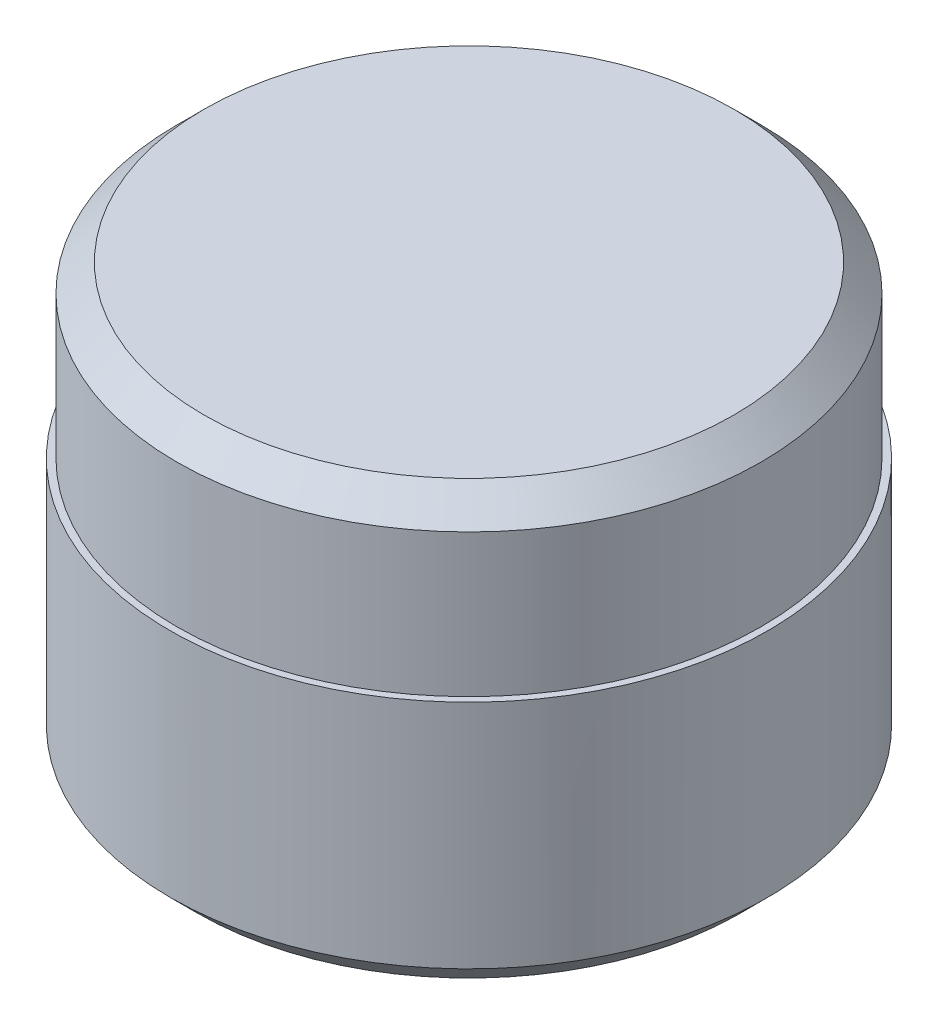
SolidWorks part; units mm, degrees
ref_plane "Front Plane" through (0, 0, 0) normal (0, 0, 1) x (1, 0, 0)
ref_plane "Top Plane" through (0, 0, 0) normal (0, 1, 0) x (1, 0, 0)
ref_plane "Right Plane" through (0, 0, 0) normal (1, 0, 0) x (0, 0, -1)
sketch "Sketch1" plane through (0, 0, 0) normal (0, 1, 0) x (1, 0, 0)
  circle A0 centre (0, 0) radius 4.4
  dimension "D1" = 8.8
extrude "Boss-Extrude1" add sketch "Sketch1" along normal blind 3.8
sketch "Sketch2" plane through (0, 3.8, 0) normal (0, 1, 0) x (1, 0, 0)
  circle A0 centre (0, 0) radius 4.3
  dimension "D1" = 8.6
extrude "Boss-Extrude2" add sketch "Sketch2" along normal blind 2.5
chamfer "Chamfer1" distance 0.4 angle 45 2 edges at (0, 0, 4.4) (0, 6.3, 4.3)
equation "\"pin_circle_R\" = 27"
equation "\"ecc\" = 1.5"
equation "\"n_pins\" = 11"
equation "\"pin_d\" = 3"
equation "\"out_pin_R\" = 18.5"
equation "\"disc_clr\" = 0.1"
equation "\"seat_6803\" = 26.1"
equation "\"disc_t\" = 5"
equation "\"out_hole_clr\" = 0.5"
equation "\"boss_17\" = 17.13"
equation "\"rotor_bolt_R\" = 10"
equation "\"m25_clr\" = 2.8"
equation "\"m25_head\" = 5"
equation "\"insert_hole\" = 4.4"
equation "\"csk\" = 0.6"
equation "\"peg_d\" = 3.0"
equation "\"plug_d\" = 8.6"
equation "\"D1@Sketch1\"=\"plug_shaft_d\""
equation "\"seat_6806\" = 42.1"
equation "\"peg_clr\" = 0.3"
equation "\"m3_clr\" = 3.4"
equation "\"m3_head\" = 6.2"
equation "\"pin_press\" = 3.2"
equation "\"pin_slip\" = 3.35"
equation "\"hub_30\" = 30.18"
equation "\"hub_short\" = 0.2"
equation "\"m3_tap\" = 2.8"
equation "\"rear_plate_t\" = 2"
equation "\"motor_ring\" = 40.4"
equation "\"plug_shaft_d\" = 8.8"
equation "\"D1@Sketch2\"=\"plug_d\""
